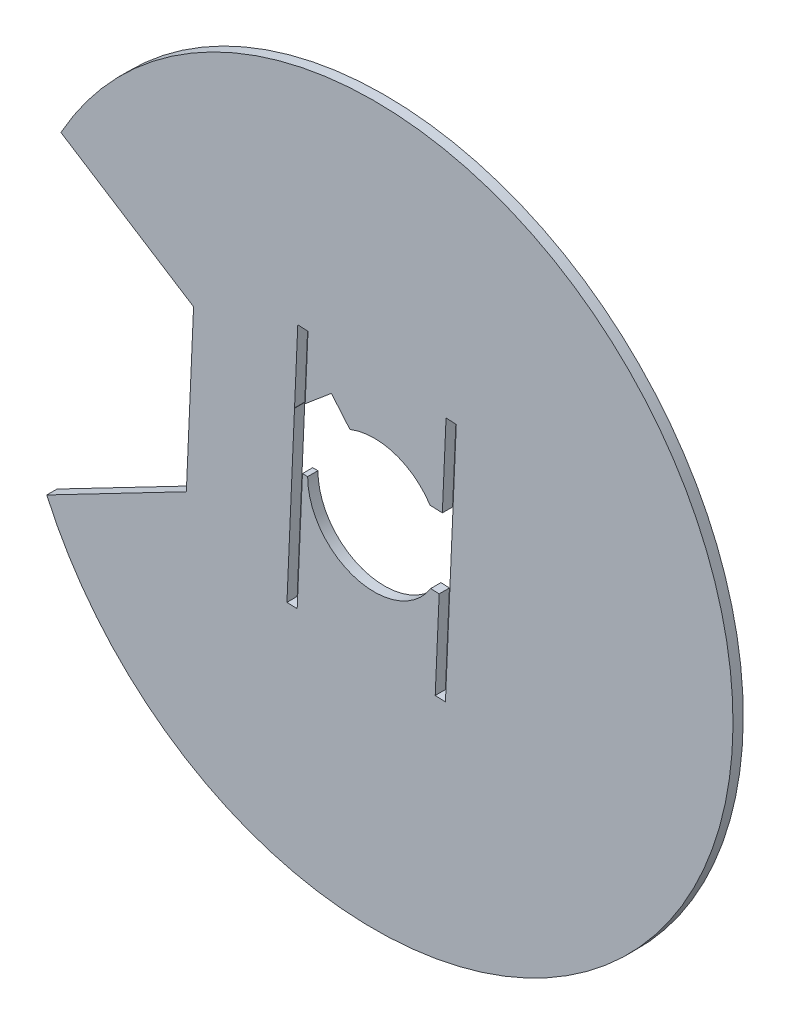
SolidWorks part; units mm, degrees
material "Balsa"
ref_plane "Plan de face" through (0, 0, 0) normal (0, 0, 1) x (1, 0, 0)
ref_plane "Plan de dessus" through (0, 0, 0) normal (0, 1, 0) x (1, 0, 0)
ref_plane "Plan de droite" through (0, 0, 0) normal (1, 0, 0) x (0, 0, -1)
sketch "Esquisse1" plane through (0, 0, 0) normal (0, 0, 1) x (1, 0, 0)
  line L0 (-11.9, 30.243) -> (-20.9197, 40.9503)
  line L1 (0, 0) -> (31.6699, 0) construction
  line L2 (-20.9197, 40.9503) -> (-33.7021, 30.1824)
  line L4 (0, 0) -> (0, 32.5) construction
  line L5 (35.6001, -41.61) -> (34.7183, -61.5906) construction
  line L6 (-41.7246, -38.1976) -> (-36.7295, -38.418) construction
  line L7 (-41.7246, -38.1976) -> (-41.2837, -28.2073) construction
  line L8 (-41.2837, -28.2073) -> (-36.2886, -28.4277) construction
  line L9 (-36.7295, -38.418) -> (-36.2886, -28.4277) construction
  line L10 (34.7183, -61.5906) -> (40.0089, 58.2928)
  line L11 (-38.9773, 25.7386) -> (-11.9, 30.243) construction
  line L12 (-29.9576, 15.0314) -> (-20.9197, 40.9503) construction
  line L13 (0, 0) -> (-25.4386, 27.9908) construction
  line L14 (34.7183, -61.5906) -> (29.7232, -61.3701)
  line L15 (40.0089, 58.2928) -> (35.0138, 58.5132)
  line L16 (30.605, -41.3896) -> (35.6001, -41.61) construction
  line L17 (30.605, -41.3896) -> (31.0459, -31.3993) construction
  line L18 (35.6001, -41.61) -> (36.041, -31.6197) construction
  line L19 (31.0459, -31.3993) -> (36.041, -31.6197) construction
  line L20 (29.7232, -61.3701) -> (31.6607, -17.466)
  line L21 (-37.6113, -58.3986) -> (-42.6064, -58.1781)
  line L22 (-37.6113, -58.3986) -> (-35.0341, 0)
  line L23 (-42.6064, -58.1781) -> (-37.3158, 61.7052)
  line L24 (39.1272, 38.3122) -> (34.132, 38.5327) construction
  line L25 (39.1272, 38.3122) -> (38.6863, 28.3219) construction
  line L26 (34.132, 38.5327) -> (33.6911, 28.5424) construction
  line L27 (38.6863, 28.3219) -> (33.6911, 28.5424) construction
  line L28 (-32.3207, 61.4847) -> (-37.3158, 61.7052)
  line L29 (-38.9068, 25.6548) -> (-38.9773, 25.7386)
  line L30 (-38.9002, 25.8036) -> (-38.9773, 25.7386)
  line L31 (-33.7021, 30.1824) -> (-32.3207, 61.4847)
  line L32 (-33.2024, 41.5042) -> (-38.1976, 41.7246) construction
  line L33 (-33.2024, 41.5042) -> (-33.6433, 31.5139) construction
  line L34 (-38.1976, 41.7246) -> (-38.6385, 31.7344) construction
  line L35 (-33.6433, 31.5139) -> (-38.6385, 31.7344) construction
  line L36 (33.2038, 17.5) -> (35.0138, 58.5132)
  line L37 (-32.5, 0) -> (-35.0341, 0)
  line L38 (27.2154, 17.7643) -> (33.2038, 17.5)
  line L39 (27.5233, -17.2834) -> (31.6607, -17.466)
  line L40 (-38.1976, 41.7246) -> (39.1272, 38.3122) construction
  line L41 (-38.1976, 41.7246) -> (-41.7246, -38.1976) construction
  line L42 (39.1272, 38.3122) -> (35.6001, -41.61) construction
  line L43 (-41.7246, -38.1976) -> (35.6001, -41.61) construction
  circle A0 centre (0, 0) radius 175
  arc A1 (-32.5, 0) -> (27.5233, -17.2834) centre (0, 0) ccw
  arc A2 (27.2154, 17.7643) -> (-11.9, 30.243) centre (0, 0) ccw
  dimension "D1" = 65
  dimension "D10" = 350
  dimension "D2" = 87.845
  dimension "D3" = 42.265
  dimension "D4" = 14
  dimension "D5" = 10
  dimension "D6" = 57.18
  dimension "D7" = 5
  dimension "D8" = 20
  dimension "D9" = 20
  dimension "D11" = 35
  dimension "D12" = 17.5
extrude "Boss.-Extru.1" add sketch "Esquisse1" along normal blind 5 contours A0 A2 L36 L15 L10 L14 L20 A1 L22 L21 L23 L29 L30 L28 L31 L2 L0 region at (-170.0503, 0, 0)
sketch "Esquisse2" plane through (0, 0, 5) normal (0, 0, 1) x (1, 0, 0)
  line L0 (-88.149, 43.929) -> (-152.8606, 85.1976)
  line L1 (-88.149, 43.929) -> (-91.676, -35.9932)
  line L2 (-91.676, -35.9932) -> (-159.7715, -71.4008)
  line L3 (-159.7715, -71.4008) -> (-91.676, -35.9932) construction
  line L4 (-88.149, 43.929) -> (-152.8606, 85.1976) construction
  circle A0 centre (0, 0) radius 175 construction
  arc A1 (-152.8606, 85.1976) -> (-159.7715, -71.4008) centre (0, 0) ccw
extrude "Enlèv. mat.-Extru.1" cut sketch "Esquisse2" against normal blind 10
